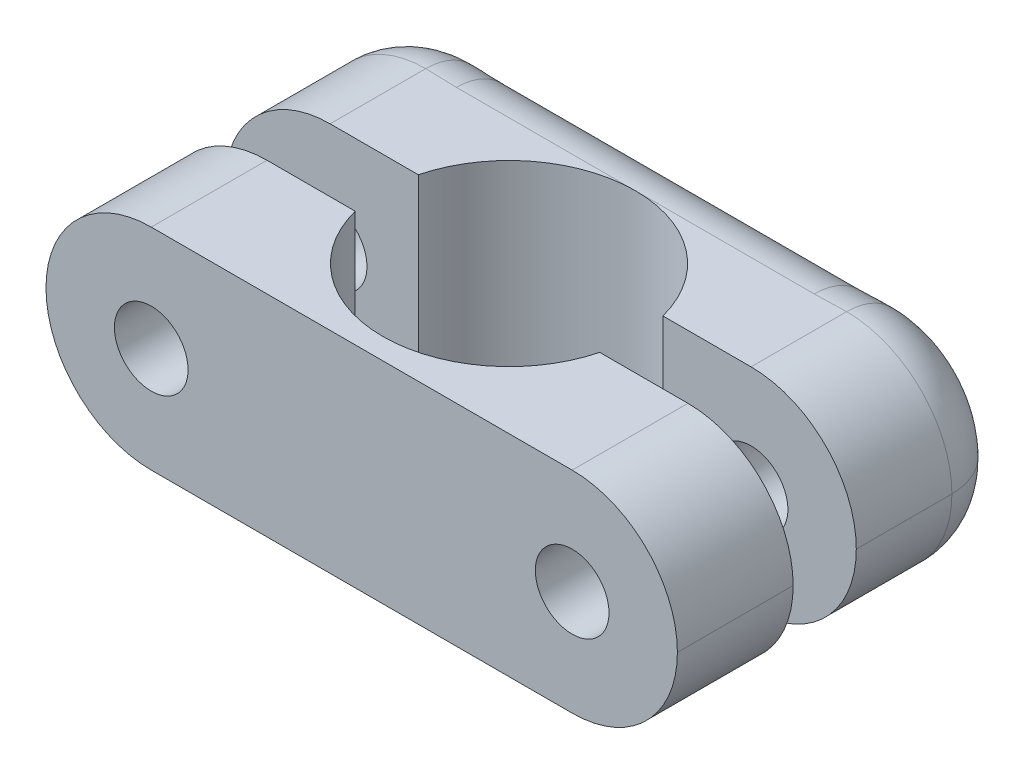
SolidWorks part; units mm, degrees
material "ABS"
ref_plane "Front Plane" through (0, 0, 0) normal (0, 0, 1) x (1, 0, 0)
ref_plane "Top Plane" through (0, 0, 0) normal (0, 1, 0) x (1, 0, 0)
ref_plane "Right Plane" through (0, 0, 0) normal (1, 0, 0) x (0, 0, -1)
sketch "Sketch1" plane through (0, 0, 0) normal (0, 1, 0) x (1, 0, 0)
  line L1 (-15, -9) -> (15, -9)
  line L2 (-15, -9) -> (-15, 9)
  line L3 (-15, 9) -> (15, 9)
  line L4 (15, -9) -> (15, 9)
  line L5 (-15, -9) -> (15, 9) construction
  line L6 (-15, 9) -> (15, -9) construction
  point P0 (0, 0)
  dimension "D1" = 30
  dimension "D2" = 18
extrude "Boss-Extrude1" add sketch "Sketch1" along normal blind 10
sketch "Sketch2" plane through (0, 10, 0) normal (0, 1, 0) x (1, 0, 0)
  circle A0 centre (0, 0) radius 6
  dimension "D1" = 12
extrude "Cut-Extrude1" cut sketch "Sketch2" against normal blind 10
sketch "Sketch3" plane through (0, 0, 9) normal (0, 0, 1) x (1, 0, 0)
  line L0 (-15, 0) -> (15, 0) construction
  line L1 (-15, 10) -> (-15, 0) construction
  circle A0 centre (-10, 5) radius 1.75
  circle A1 centre (10, 5) radius 1.75
  dimension "D1" = 3.5
  dimension "D5" = 3.5
  dimension "D2" = 5
  dimension "D3" = 5
  dimension "D4" = 20
extrude "Cut-Extrude2" cut sketch "Sketch3" against normal through all
sketch "Sketch4" plane through (0, 0, -9) normal (0, 0, -1) x (-1, 0, 0)
  circle A0 centre (-10, 5) radius 2.5
  circle A1 centre (10, 5) radius 2.5
  dimension "D1" = 5
  dimension "D2" = 5
extrude "Cut-Extrude3" cut sketch "Sketch4" against normal blind 3.5
sketch "Sketch5" plane through (0, 10, 0) normal (0, 1, 0) x (1, 0, 0)
  line L0 (-15, 9) -> (-15, -9) construction
  line L1 (15, 1.5) -> (-15, 1.5)
  line L2 (15, 1.5) -> (15, -1.5)
  line L3 (15, -1.5) -> (-15, -1.5)
  line L4 (-15, 1.5) -> (-15, -1.5)
  line L5 (15, 1.5) -> (-15, -1.5) construction
  line L6 (15, -1.5) -> (-15, 1.5) construction
  point P0 (0, 0)
  dimension "D1" = 3
extrude "Cut-Extrude4" cut sketch "Sketch5" against normal through all
sketch "Sketch9" plane through (0, 10, 0) normal (0, 1, 0) x (1, 0, 0)
  line L0 (15, -9) -> (15, -1.5) construction
  line L1 (-15, -9) -> (15, -9)
  line L2 (-15, -9) -> (-15, -7)
  line L3 (-15, -7) -> (15, -7)
  line L4 (15, -9) -> (15, -7)
  dimension "D1" = 2
extrude "Cut-Extrude5" cut sketch "Sketch9" against normal through all
fillet "Fillet3" radius 5 4 edges at (15, 10, 4.25) (15, 0, 4.25) (-15, 0, 4.25) (-15, 10, 4.25)
fillet "Fillet4" radius 5 4 edges at (15, 0, -5.25) (15, 10, -5.25) (-15, 0, -5.25) (-15, 10, -5.25)
fillet "Fillet2" radius 3 4 edges at (0, 10, -9) (0, 0, -9) (13.5355, 8.5355, -9) (-13.5355, 8.5355, -9)
